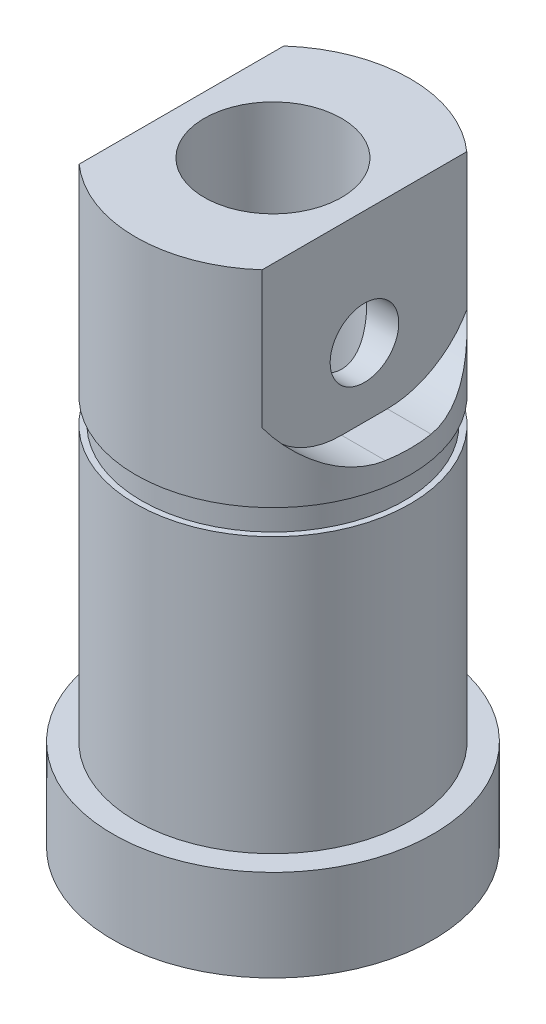
SolidWorks part; units mm, degrees
ref_plane "Front Plane" through (0, 0, 0) normal (0, 0, 1) x (1, 0, 0)
ref_plane "Top Plane" through (0, 0, 0) normal (0, 1, 0) x (1, 0, 0)
ref_plane "Right Plane" through (0, 0, 0) normal (1, 0, 0) x (0, 0, -1)
sketch "Sketch2" plane through (0, 0, 0) normal (0, 0, 1) x (1, 0, 0)
  line L0 (0, 0) -> (0, 26.1) construction
  line L19 (-3, 26.1) -> (-6, 26.1)
  line L20 (-6, 26.1) -> (-6, 17.1)
  line L21 (-6, 17.1) -> (-5.75, 17.1)
  line L22 (-5.75, 17.1) -> (-5.75, 16)
  line L23 (-5.75, 16) -> (-6, 16)
  line L24 (-6, 16) -> (-6, 4)
  line L25 (-6, 4) -> (-7, 4)
  line L26 (-7, 4) -> (-7, 0)
  line L27 (-7, 0) -> (-5, 0)
  line L28 (-5, 0) -> (-5, 1.8)
  line L29 (-5, 1.8) -> (-3, 1.8)
  line L30 (-3, 1.8) -> (-3, 26.1)
  line L40 (-6, 4) -> (-10.5, 4) construction
  line L41 (-6, 4) -> (-6, 9) construction
  line L42 (-6, 9) -> (-10.5, 9) construction
  line L43 (-10.5, 4) -> (-10.5, 9) construction
  line L44 (-6, 16) -> (-10.5, 16) construction
  line L45 (-6, 16) -> (-6, 11) construction
  line L46 (-6, 11) -> (-10.5, 11) construction
  line L47 (-10.5, 16) -> (-10.5, 11) construction
  point P22 (-13.3361, 37.8808)
  point P23 (0, 49.0482)
  point P24 (-4.0334, 26.5878)
  point P25 (-4.9274, 26.1408)
  point P26 (-3.0755, 27.0348)
  point P27 (-7, 25.6938)
  point P28 (-7, 15.6783)
  dimension "D1" = 12
  dimension "D2" = 10.5
  dimension "D3" = 5
  dimension "D4" = 5
  dimension "D5" = 14
  dimension "D6" = 10
  dimension "D7" = 6
  dimension "D8" = 1.8
  dimension "D9" = 1.1
  dimension "D10" = 11.5
  dimension "D11" = 9
  dimension "D12" = 4
  dimension "D13" = 12
revolve "Revolve1" add sketch "Sketch2" angle 360 about L0
ref_plane "Plane1" through (-6, 0, 0) normal (-1, 0, 0) x (0, 0, 1)
sketch "Sketch3" plane through (-6, 0, 0) normal (-1, 0, 0) x (0, 0, 1)
  line L0 (0, 26.1) -> (0, 9.9472) construction
  line L1 (6, 26.1) -> (-6, 26.1) construction
  line L2 (9, 26.1) -> (-9, 26.1)
  line L3 (-1, 18.1) -> (1, 18.1)
  arc A0 (-9, 26.1) -> (-5, 22.1) centre (-9, 22.1) cw
  arc A1 (-5, 22.1) -> (-1, 18.1) centre (-1, 22.1) ccw
  arc A2 (9, 26.1) -> (5, 22.1) centre (9, 22.1) ccw
  arc A3 (5, 22.1) -> (1, 18.1) centre (1, 22.1) cw
  point P13 (0, 18.1)
  dimension "D1" = 1
  dimension "D2" = 8
  dimension "D3" = 4
  dimension "D4" = 4
  dimension "D5" = 8
extrude "Cut-Extrude2" cut sketch "Sketch3" against normal blind 2 contours A0 A1 L3 A3 A2 L2
mirror "Mirror1" about plane through (0, 0, 0) normal (1, 0, 0) of "Cut-Extrude2"
sketch "Sketch4" plane through (-4, 0, 0) normal (-1, 0, 0) x (0, 0, 1)
  line L0 (1, 18.1) -> (-1, 18.1) construction
  circle A0 centre (0, 21.1) radius 1.5
  point P2 (0, 0)
  point P5 (0, 18.1)
  dimension "D1" = 3
  dimension "D2" = 3
extrude "Cut-Extrude3" cut sketch "Sketch4" against normal through all contours A0
